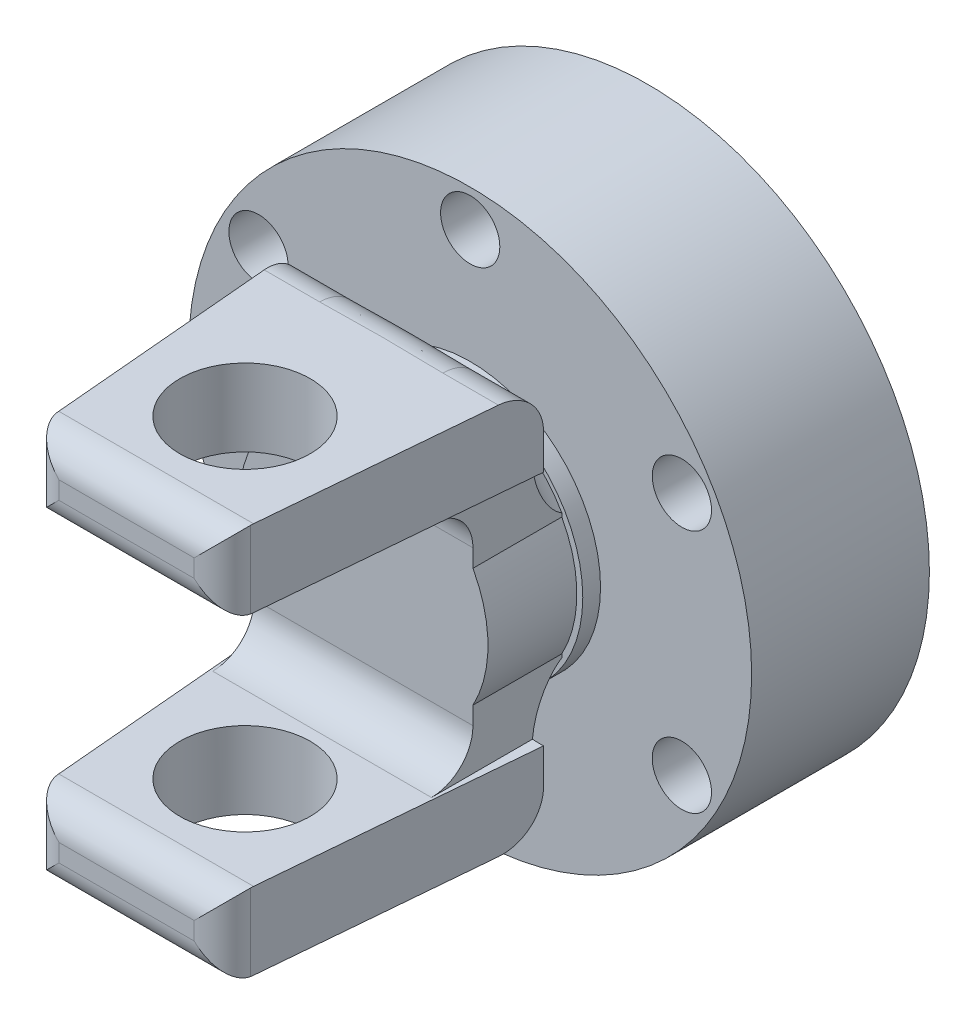
SolidWorks part; units mm, degrees
ref_plane "Płaszczyzna przednia" through (0, 0, 0) normal (0, 0, 1) x (1, 0, 0)
ref_plane "Płaszczyzna górna" through (0, 0, 0) normal (0, 1, 0) x (1, 0, 0)
ref_plane "Płaszczyzna prawa" through (0, 0, 0) normal (1, 0, 0) x (0, 0, -1)
sketch "Szkic1" plane through (0, 0, 0) normal (0, 0, 1) x (1, 0, 0)
  circle A0 centre (0, 0) radius 47.5
  dimension "D1" = 95
extrude "Dodanie-wyciągnięcie1" add sketch "Szkic1" along normal blind 30 contours A0
sketch "Szkic2" plane through (0, 0, 30) normal (0, 0, 1) x (1, 0, 0)
  circle A0 centre (0, 41.25) radius 5
  dimension "D1" = 10
  dimension "D2" = 41.25
extrude "Wytnij-wyciągnięcie1" cut sketch "Szkic2" against normal up to next
pattern_circular "Szyk kołowy1" count 6 over 360 about axis through (0, 0, 30) along (0, 0, 1) of "Wytnij-wyciągnięcie1"
sketch "Szkic3" plane through (0, 0, 30) normal (0, 0, 1) x (1, 0, 0)
  circle A0 centre (0, 0) radius 21
  dimension "D1" = 42
extrude "Dodanie-wyciągnięcie2" add sketch "Szkic3" along normal blind 0.001
sketch "Szkic5" plane through (0, 0, 30.001) normal (0, 0, 1) x (1, 0, 0)
  circle A0 centre (0, 0) radius 22
  dimension "D1" = 44
extrude "Dodanie-wyciągnięcie4" add sketch "Szkic5" along normal blind 3
sketch "Szkic7" plane through (0, 0, 33.001) normal (0, 0, 1) x (1, 0, 0)
  circle A0 centre (0, 0) radius 21 construction
  circle A1 centre (0, 0) radius 21
extrude "Dodanie-wyciągnięcie5" add sketch "Szkic7" along normal blind 15
ref_plane "Płaszczyzna2" through (0, 26.5, 0) normal (0, 1, 0) x (1, 0, 0)
sketch "Szkic9" plane through (0, 26.5, 0) normal (0, 1, 0) x (1, 0, 0)
  line L0 (-20.3744, -38.001) -> (-16, -88.001)
  line L1 (-16, -88.001) -> (16, -88.001)
  line L2 (16, -88.001) -> (20.3744, -38.001)
  line L3 (20.3744, -38.001) -> (-20.3744, -38.001)
  line L4 (-21, -48.001) -> (21, -48.001) construction
  point P2 (16.0392, -76.8034)
  point P7 (0, -88.001)
  dimension "D1" = 50
  dimension "D2" = 32
  dimension "D3" = 95
  dimension "D4" = 95
  dimension "D5" = 10
extrude "Dodanie-wyciągnięcie6" add sketch "Szkic9" along normal mid plane 13 contours L1 L2 L3 L0
ref_plane "Płaszczyzna3" through (0, 10, 0) normal (0, 1, 0) x (1, 0, 0)
sketch "Szkic14" plane through (0, 10, 0) normal (0, 1, 0) x (1, 0, 0)
  line L1 (-18.4662, -38.001) -> (18.4662, -38.001)
  line L2 (-18.4662, -38.001) -> (-18.4662, -48.001)
  line L3 (-18.4662, -48.001) -> (18.4662, -48.001)
  line L4 (18.4662, -38.001) -> (18.4662, -48.001)
  point P4 (0, 0)
  point P5 (0, 0)
  point P6 (0, 0)
  point P7 (0, 0)
  point P13 (0, 0)
  dimension "D1" = 10
extrude "Dodanie-wyciągnięcie7" add sketch "Szkic14" along normal up to next (23 mm away)
fillet "Zaokrąglenie1" radius 7 2 edges at (0, 21, 38.001) (0, 20, 48.001)
fillet "Zaokrąglenie2" radius 7 1 edges at (0, 33, 38.001)
fillet "Zaokrąglenie3" radius 5 4 edges at (-16, 26.5, 88.001) (0, 33, 88.001) (16, 26.5, 88.001) (0, 20, 88.001)
sketch "Szkic16" plane through (0, 33, 0) normal (0, 1, 0) x (1, 0, 0)
  line L0 (11.4183, -88.001) -> (-11.4183, -88.001) construction
  circle A0 centre (0, -68.001) radius 11
  dimension "D1" = 22
  dimension "D2" = 20
extrude "Wytnij-wyciągnięcie2" cut sketch "Szkic16" against normal up to next contours A0
mirror "Lustro1" about plane through (0, 0, 0) normal (0, 1, 0) of "Dodanie-wyciągnięcie7", "Zaokrąglenie1", "Zaokrąglenie2", "Zaokrąglenie3", "Dodanie-wyciągnięcie6", "Wytnij-wyciągnięcie2"
